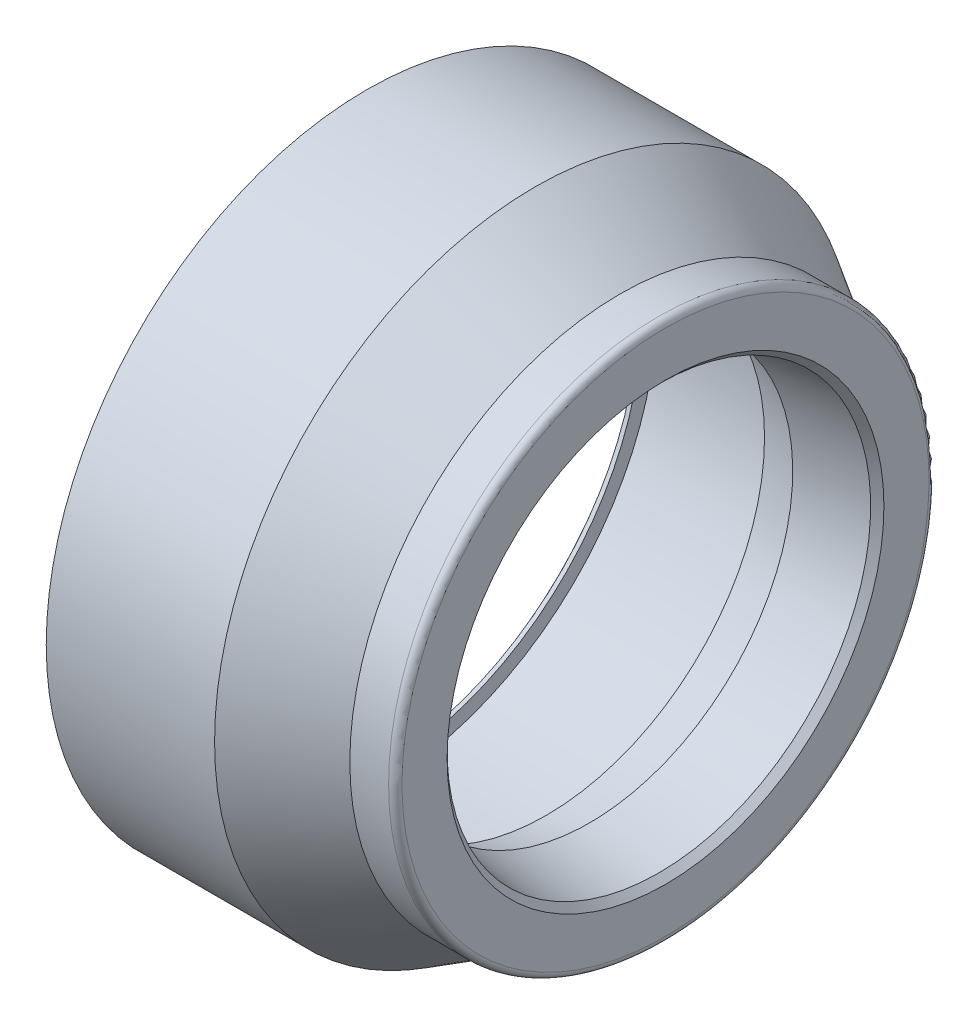
SolidWorks part; units mm, degrees
ref_plane "Front Plane" through (0, 0, 0) normal (0, 0, 1) x (1, 0, 0)
ref_plane "Top Plane" through (0, 0, 0) normal (0, 1, 0) x (1, 0, 0)
ref_plane "Right Plane" through (0, 0, 0) normal (1, 0, 0) x (0, 0, -1)
sketch "Sketch1" plane through (0, 0, 0) normal (0, 0, 1) x (1, 0, 0)
  line L0 (14.0477, 0) -> (14.0477, 22.86) construction
  line L1 (0, 3.7871) -> (-2.5126, 1.2745)
  line L2 (0, 3.7871) -> (0, 20.8736)
  line L3 (-2.54, 23.4136) -> (-17.2089, 23.4136)
  line L4 (-17.2089, 23.4136) -> (-49.3872, 42.4416)
  line L5 (-49.3872, 42.4416) -> (-113.1242, 42.4416)
  line L6 (-2.5126, 1.2745) -> (-28.748, -1.9913)
  line L7 (-28.748, -1.9913) -> (-28.748, 1.2745)
  line L8 (-28.748, 1.2745) -> (-45.139, 3.7249)
  line L9 (-45.139, 3.7249) -> (-45.139, 23.7782)
  line L10 (-47.679, 26.3182) -> (-108.5198, 26.3182)
  line L11 (-113.1242, 42.4416) -> (-113.1242, 25.0008)
  line L12 (-113.1242, 25.0008) -> (-110.6362, 24.9079)
  line L13 (-110.6362, 24.9079) -> (-110.1283, 20.8277)
  line L14 (-110.1283, 20.8277) -> (-108.5198, 20.8277)
  line L15 (-108.5198, 20.8277) -> (-108.5198, 26.3182)
  line L16 (-3.8865, 1.1035) -> (-3.8865, -78.9065) construction
  line L17 (-3.8865, -78.9065) -> (-126.7969, -78.9065) construction
  arc A0 (0, 20.8736) -> (-2.54, 23.4136) centre (-2.54, 20.8736) ccw
  arc A1 (-47.679, 26.3182) -> (-45.139, 23.7782) centre (-47.679, 23.7782) cw
  point P12 (0, 0)
  point P24 (-108.4339, 19.7542)
  point P25 (-110.0471, 19.8278)
  point P28 (-111.3086, 20.7648)
  point P29 (0, 0)
  point P30 (-45.6638, 19.3002)
  point P31 (-109.6519, 22.9253)
  point P32 (0, 0)
  point P33 (-113.1242, 20.2501)
  point P34 (0, 0)
  point P35 (-109.0446, 23.7203)
  point P36 (-111.1607, 22.3828)
  point P37 (-29.9768, 39.438)
  point P38 (-19.6995, 27.3985)
  point P39 (-17.2089, 23.4136)
  point P40 (-49.3872, 42.4416)
  dimension "D2" = 2.54
  dimension "D3" = 2.54
  dimension "D1" = 22.86
  dimension "D4" = 80.01
revolve "Revolve1" add sketch "Sketch1" angle 360 about L17
